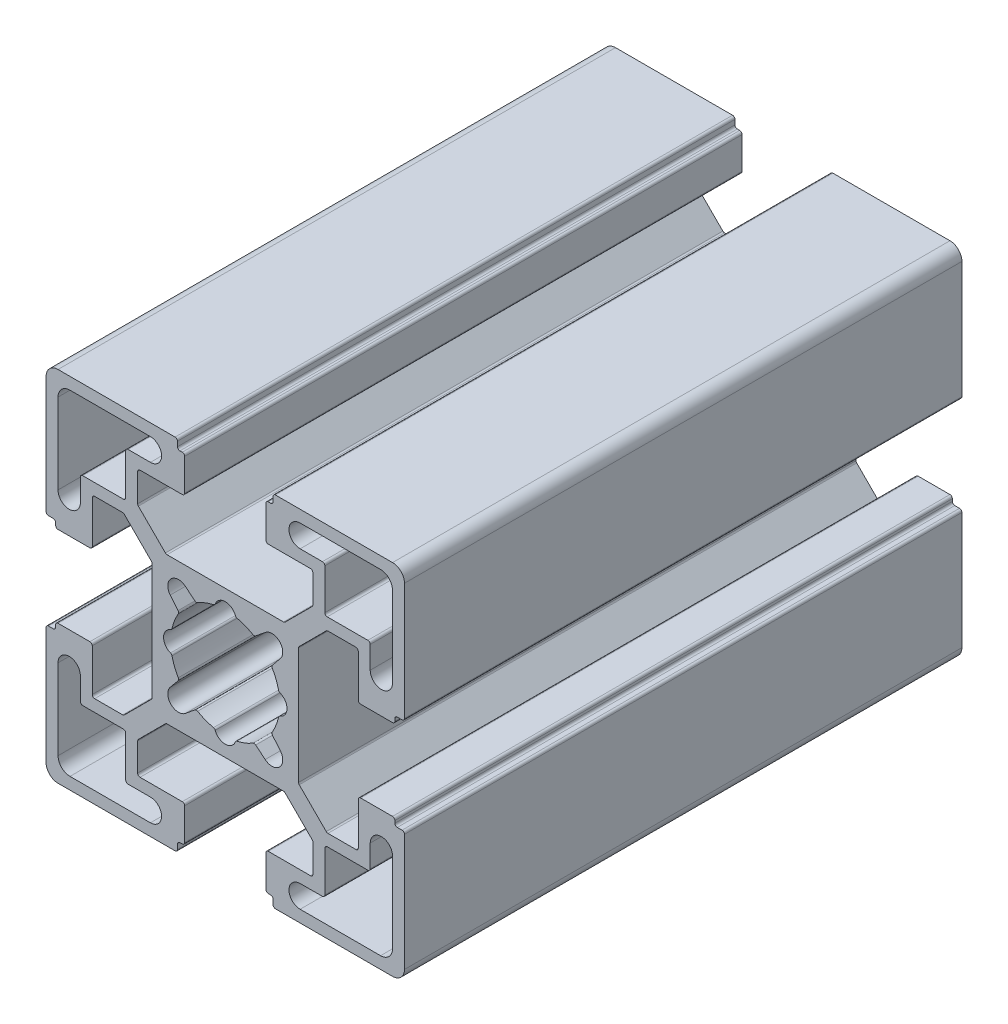
SolidWorks part; units mm, degrees
material "6063-T5"
ref_plane "Plane1" through (0, 0, 0) normal (0, 0, 1) x (1, 0, 0)
ref_plane "Plane2" through (0, 0, 0) normal (0, 1, 0) x (1, 0, 0)
ref_plane "Plane3" through (0, 0, 0) normal (1, 0, 0) x (0, 0, -1)
sketch "Sketch1" plane through (0, 0, 0) normal (0, 0, 1) x (1, 0, 0)
  line L0 (-3.8182, 5.9298) -> (-5.0112, 6.9114)
  line L1 (-6.9114, 5.0112) -> (-5.9298, 3.8182)
  line L2 (-5.9298, -3.8182) -> (-6.9114, -5.0112)
  line L3 (-5.0112, -6.9114) -> (-3.8182, -5.9298)
  line L4 (3.8182, -5.9298) -> (5.0112, -6.9114)
  line L5 (6.9114, -5.0112) -> (5.9298, -3.8182)
  line L6 (5.9298, 3.8182) -> (6.9114, 5.0112)
  line L7 (5.0112, 6.9114) -> (3.8182, 5.9298)
  line L8 (-19.5, -21) -> (-9.4, -21)
  line L9 (-9.4, -18.2) -> (-12.2, -18.2)
  line L10 (-12.5, -17.9) -> (-12.5, -12.8)
  line L11 (-12.8, -12.5) -> (-17.9, -12.5)
  line L12 (-18.2, -12.2) -> (-18.2, -9.4)
  line L13 (-21, -9.4) -> (-21, -19.5)
  line L14 (17.9, -12.5) -> (12.8, -12.5)
  line L15 (12.5, -12.8) -> (12.5, -17.9)
  line L16 (12.2, -18.2) -> (9.4, -18.2)
  line L17 (9.4, -21) -> (19.5, -21)
  line L18 (21, -19.5) -> (21, -9.4)
  line L19 (18.2, -9.4) -> (18.2, -12.2)
  line L20 (19.5, 21) -> (9.4, 21)
  line L21 (9.4, 18.2) -> (12.2, 18.2)
  line L22 (12.5, 17.9) -> (12.5, 12.8)
  line L23 (12.8, 12.5) -> (17.9, 12.5)
  line L24 (18.2, 12.2) -> (18.2, 9.4)
  line L25 (21, 9.4) -> (21, 19.5)
  line L26 (-18.2, 9.4) -> (-18.2, 12.2)
  line L27 (-17.9, 12.5) -> (-12.8, 12.5)
  line L28 (-12.5, 12.8) -> (-12.5, 17.9)
  line L29 (-12.2, 18.2) -> (-9.4, 18.2)
  line L30 (-9.4, 21) -> (-19.5, 21)
  line L31 (-21, 19.5) -> (-21, 9.4)
  line L32 (22.5, 6.3) -> (22.5, 21)
  line L33 (21.6, 6) -> (22.2, 6)
  line L34 (21.3, 5.4) -> (21.3, 5.7)
  line L36 (16.7, 10.7) -> (16.7, 5.4)
  line L37 (12.892, 11) -> (16.4, 11)
  line L38 (9.2879, 7.5201) -> (12.6799, 10.9121)
  line L39 (9.2, -7.308) -> (9.2, 7.308)
  line L40 (12.6799, -10.9121) -> (9.2879, -7.5201)
  line L41 (16.4, -11) -> (12.892, -11)
  line L42 (16.7, -5.4) -> (16.7, -10.7)
  line L44 (21.3, -5.7) -> (21.3, -5.4)
  line L45 (22.2, -6) -> (21.6, -6)
  line L46 (22.5, -21) -> (22.5, -6.3)
  line L47 (6.3, -22.5) -> (21, -22.5)
  line L48 (6, -21.6) -> (6, -22.2)
  line L49 (5.4, -21.3) -> (5.7, -21.3)
  line L51 (10.7, -16.7) -> (5.4, -16.7)
  line L52 (11, -12.892) -> (11, -16.4)
  line L53 (7.5201, -9.2879) -> (10.9121, -12.6799)
  line L54 (-7.4322, -9.2) -> (7.308, -9.2)
  line L55 (-10.9121, -12.6799) -> (-7.4322, -9.2)
  line L56 (-11, -16.4) -> (-11, -12.892)
  line L57 (-5.4, -16.7) -> (-10.7, -16.7)
  line L59 (-5.7, -21.3) -> (-5.4, -21.3)
  line L60 (-6, -22.2) -> (-6, -21.6)
  line L61 (-21, -22.5) -> (-6.3, -22.5)
  line L62 (-22.5, -6.3) -> (-22.5, -21)
  line L63 (-21.6, -6) -> (-22.2, -6)
  line L64 (-21.3, -5.4) -> (-21.3, -5.7)
  line L66 (-16.7, -10.7) -> (-16.7, -5.4)
  line L67 (-12.892, -11) -> (-16.4, -11)
  line L68 (-9.2879, -7.5201) -> (-12.6799, -10.9121)
  line L69 (-9.2, 7.308) -> (-9.2, -7.308)
  line L70 (-12.6799, 10.9121) -> (-9.2879, 7.5201)
  line L71 (-16.4, 11) -> (-12.892, 11)
  line L72 (-16.7, 5.4) -> (-16.7, 10.7)
  line L74 (-21.3, 5.7) -> (-21.3, 5.4)
  line L75 (-22.2, 6) -> (-21.6, 6)
  line L76 (-22.5, 21) -> (-22.5, 6.3)
  line L77 (-6.3, 22.5) -> (-21, 22.5)
  line L78 (-6, 21.6) -> (-6, 22.2)
  line L79 (-5.4, 21.3) -> (-5.7, 21.3)
  line L81 (-10.7, 16.7) -> (-5.4, 16.7)
  line L82 (-11, 12.892) -> (-11, 16.4)
  line L83 (-7.5201, 9.2879) -> (-10.9121, 12.6799)
  line L84 (7.308, 9.2) -> (-7.308, 9.2)
  line L85 (10.9121, 12.6799) -> (7.5201, 9.2879)
  line L86 (11, 16.4) -> (11, 12.892)
  line L87 (5.4, 16.7) -> (10.7, 16.7)
  line L89 (5.7, 21.3) -> (5.4, 21.3)
  line L90 (6, 22.2) -> (6, 21.6)
  line L91 (21, 22.5) -> (6.3, 22.5)
  line L92 (-5.1, 17) -> (-5.1, 21)
  line L93 (-21, 5.1) -> (-17, 5.1)
  line L94 (-17, -5.1) -> (-21, -5.1)
  line L95 (-5.1, -21) -> (-5.1, -17)
  line L96 (5.1, -17) -> (5.1, -21)
  line L97 (21, -5.1) -> (17, -5.1)
  line L98 (17, 5.1) -> (21, 5.1)
  line L99 (5.1, 21) -> (5.1, 17)
  arc A0 (-1.4794, 6.6883) -> (-1.2635, 6.8756) centre (-1.5442, 6.9813) ccw
  arc A1 (-1.4794, 6.6883) -> (-3.4754, 5.9029) centre (0, 0) ccw
  arc A2 (-3.8182, 5.9298) -> (-3.4754, 5.9029) centre (-3.6276, 6.1614) ccw
  arc A3 (-5.0112, 6.9114) -> (-6.9114, 5.0112) centre (-5.869, 5.869) ccw
  arc A4 (-5.9029, 3.4754) -> (-5.9298, 3.8182) centre (-6.1614, 3.6276) ccw
  arc A5 (-5.9029, 3.4754) -> (-6.6883, 1.4794) centre (0, 0) ccw
  arc A6 (-6.8756, 1.2635) -> (-6.6883, 1.4794) centre (-6.9813, 1.5442) ccw
  arc A7 (-6.8756, 1.2635) -> (-6.8756, -1.2635) centre (-6.4, 0) ccw
  arc A8 (-6.6883, -1.4794) -> (-6.8756, -1.2635) centre (-6.9813, -1.5442) ccw
  arc A9 (-6.6883, -1.4794) -> (-5.9029, -3.4754) centre (0, 0) ccw
  arc A10 (-5.9298, -3.8182) -> (-5.9029, -3.4754) centre (-6.1614, -3.6276) ccw
  arc A11 (-6.9114, -5.0112) -> (-5.0112, -6.9114) centre (-5.869, -5.869) ccw
  arc A12 (-3.4754, -5.9029) -> (-3.8182, -5.9298) centre (-3.6276, -6.1614) ccw
  arc A13 (-3.4754, -5.9029) -> (-1.4794, -6.6883) centre (0, 0) ccw
  arc A14 (-1.2635, -6.8756) -> (-1.4794, -6.6883) centre (-1.5442, -6.9812) ccw
  arc A15 (-1.2635, -6.8756) -> (1.2635, -6.8756) centre (0, -6.4) ccw
  arc A16 (1.4794, -6.6883) -> (1.2635, -6.8756) centre (1.5442, -6.9812) ccw
  arc A17 (1.4794, -6.6883) -> (3.4754, -5.9029) centre (0, 0) ccw
  arc A18 (3.8182, -5.9298) -> (3.4754, -5.9029) centre (3.6276, -6.1614) ccw
  arc A19 (5.0112, -6.9114) -> (6.9114, -5.0112) centre (5.869, -5.869) ccw
  arc A20 (5.9029, -3.4754) -> (5.9298, -3.8182) centre (6.1614, -3.6276) ccw
  arc A21 (5.9029, -3.4754) -> (6.6883, -1.4794) centre (0, 0) ccw
  arc A22 (6.8756, -1.2635) -> (6.6883, -1.4794) centre (6.9812, -1.5442) ccw
  arc A23 (6.8756, -1.2635) -> (6.8756, 1.2635) centre (6.4, 0) ccw
  arc A24 (6.6883, 1.4794) -> (6.8756, 1.2635) centre (6.9812, 1.5442) ccw
  arc A25 (6.6883, 1.4794) -> (5.9029, 3.4754) centre (0, 0) ccw
  arc A26 (5.9298, 3.8182) -> (5.9029, 3.4754) centre (6.1614, 3.6276) ccw
  arc A27 (6.9114, 5.0112) -> (5.0112, 6.9114) centre (5.869, 5.869) ccw
  arc A28 (3.4754, 5.9029) -> (3.8182, 5.9298) centre (3.6276, 6.1614) ccw
  arc A29 (3.4754, 5.9029) -> (1.4794, 6.6883) centre (0, 0) ccw
  arc A30 (1.2635, 6.8756) -> (1.4794, 6.6883) centre (1.5442, 6.9813) ccw
  arc A31 (1.2635, 6.8756) -> (-1.2635, 6.8756) centre (0, 6.4) ccw
  arc A32 (-21, -19.5) -> (-19.5, -21) centre (-19.5, -19.5) ccw
  arc A33 (-9.4, -21) -> (-9.4, -18.2) centre (-9.4, -19.6) ccw
  arc A34 (-12.5, -17.9) -> (-12.2, -18.2) centre (-12.2, -17.9) ccw
  arc A35 (-12.5, -12.8) -> (-12.8, -12.5) centre (-12.8, -12.8) ccw
  arc A36 (-18.2, -12.2) -> (-17.9, -12.5) centre (-17.9, -12.2) ccw
  arc A37 (-18.2, -9.4) -> (-21, -9.4) centre (-19.6, -9.4) ccw
  arc A38 (17.9, -12.5) -> (18.2, -12.2) centre (17.9, -12.2) ccw
  arc A39 (12.8, -12.5) -> (12.5, -12.8) centre (12.8, -12.8) ccw
  arc A40 (12.2, -18.2) -> (12.5, -17.9) centre (12.2, -17.9) ccw
  arc A41 (9.4, -18.2) -> (9.4, -21) centre (9.4, -19.6) ccw
  arc A42 (19.5, -21) -> (21, -19.5) centre (19.5, -19.5) ccw
  arc A43 (21, -9.4) -> (18.2, -9.4) centre (19.6, -9.4) ccw
  arc A44 (21, 19.5) -> (19.5, 21) centre (19.5, 19.5) ccw
  arc A45 (9.4, 21) -> (9.4, 18.2) centre (9.4, 19.6) ccw
  arc A46 (12.5, 17.9) -> (12.2, 18.2) centre (12.2, 17.9) ccw
  arc A47 (12.5, 12.8) -> (12.8, 12.5) centre (12.8, 12.8) ccw
  arc A48 (18.2, 12.2) -> (17.9, 12.5) centre (17.9, 12.2) ccw
  arc A49 (18.2, 9.4) -> (21, 9.4) centre (19.6, 9.4) ccw
  arc A50 (-21, 9.4) -> (-18.2, 9.4) centre (-19.6, 9.4) ccw
  arc A51 (-17.9, 12.5) -> (-18.2, 12.2) centre (-17.9, 12.2) ccw
  arc A52 (-12.8, 12.5) -> (-12.5, 12.8) centre (-12.8, 12.8) ccw
  arc A53 (-12.2, 18.2) -> (-12.5, 17.9) centre (-12.2, 17.9) ccw
  arc A54 (-9.4, 18.2) -> (-9.4, 21) centre (-9.4, 19.6) ccw
  arc A55 (-19.5, 21) -> (-21, 19.5) centre (-19.5, 19.5) ccw
  arc A56 (22.2, 6) -> (22.5, 6.3) centre (22.2, 6.3) ccw
  arc A57 (21.6, 6) -> (21.3, 5.7) centre (21.6, 5.7) ccw
  arc A58 (-17, -5.1) -> (-16.7, -5.4) centre (-17, -5.4) cw
  arc A59 (16.7, 10.7) -> (16.4, 11) centre (16.4, 10.7) ccw
  arc A60 (12.892, 11) -> (12.6799, 10.9121) centre (12.892, 10.7) ccw
  arc A61 (9.2879, 7.5201) -> (9.2, 7.308) centre (9.5, 7.308) ccw
  arc A62 (9.2, -7.308) -> (9.2879, -7.5201) centre (9.5, -7.308) ccw
  arc A63 (12.6799, -10.9121) -> (12.892, -11) centre (12.892, -10.7) ccw
  arc A64 (16.4, -11) -> (16.7, -10.7) centre (16.4, -10.7) ccw
  arc A65 (-17, 5.1) -> (-16.7, 5.4) centre (-17, 5.4) ccw
  arc A66 (21.3, -5.7) -> (21.6, -6) centre (21.6, -5.7) ccw
  arc A67 (22.5, -6.3) -> (22.2, -6) centre (22.2, -6.3) ccw
  arc A68 (21, -22.5) -> (22.5, -21) centre (21, -21) ccw
  arc A69 (6, -22.2) -> (6.3, -22.5) centre (6.3, -22.2) ccw
  arc A70 (6, -21.6) -> (5.7, -21.3) centre (5.7, -21.6) ccw
  arc A71 (-5.1, 17) -> (-5.4, 16.7) centre (-5.4, 17) cw
  arc A72 (10.7, -16.7) -> (11, -16.4) centre (10.7, -16.4) ccw
  arc A73 (11, -12.892) -> (10.9121, -12.6799) centre (10.7, -12.892) ccw
  arc A74 (7.5201, -9.2879) -> (7.308, -9.2) centre (7.308, -9.5) ccw
  arc A75 (-10.9121, -12.6799) -> (-11, -12.892) centre (-10.7, -12.892) ccw
  arc A76 (-11, -16.4) -> (-10.7, -16.7) centre (-10.7, -16.4) ccw
  arc A77 (5.1, 17) -> (5.4, 16.7) centre (5.4, 17) ccw
  arc A78 (-5.7, -21.3) -> (-6, -21.6) centre (-5.7, -21.6) ccw
  arc A79 (-6.3, -22.5) -> (-6, -22.2) centre (-6.3, -22.2) ccw
  arc A80 (-22.5, -21) -> (-21, -22.5) centre (-21, -21) ccw
  arc A81 (-22.2, -6) -> (-22.5, -6.3) centre (-22.2, -6.3) ccw
  arc A82 (-21.6, -6) -> (-21.3, -5.7) centre (-21.6, -5.7) ccw
  arc A83 (16.7, 5.4) -> (17, 5.1) centre (17, 5.4) ccw
  arc A84 (-16.7, -10.7) -> (-16.4, -11) centre (-16.4, -10.7) ccw
  arc A85 (-12.892, -11) -> (-12.6799, -10.9121) centre (-12.892, -10.7) ccw
  arc A86 (-9.2879, -7.5201) -> (-9.2, -7.308) centre (-9.5, -7.308) ccw
  arc A87 (-9.2, 7.308) -> (-9.2879, 7.5201) centre (-9.5, 7.308) ccw
  arc A88 (-12.6799, 10.9121) -> (-12.892, 11) centre (-12.892, 10.7) ccw
  arc A89 (-16.4, 11) -> (-16.7, 10.7) centre (-16.4, 10.7) ccw
  arc A90 (17, -5.1) -> (16.7, -5.4) centre (17, -5.4) ccw
  arc A91 (-21.3, 5.7) -> (-21.6, 6) centre (-21.6, 5.7) ccw
  arc A92 (-22.5, 6.3) -> (-22.2, 6) centre (-22.2, 6.3) ccw
  arc A93 (-21, 22.5) -> (-22.5, 21) centre (-21, 21) ccw
  arc A94 (-6, 22.2) -> (-6.3, 22.5) centre (-6.3, 22.2) ccw
  arc A95 (-6, 21.6) -> (-5.7, 21.3) centre (-5.7, 21.6) ccw
  arc A96 (5.1, -17) -> (5.4, -16.7) centre (5.4, -17) cw
  arc A97 (-10.7, 16.7) -> (-11, 16.4) centre (-10.7, 16.4) ccw
  arc A98 (-11, 12.892) -> (-10.9121, 12.6799) centre (-10.7, 12.892) ccw
  arc A99 (-7.5201, 9.2879) -> (-7.308, 9.2) centre (-7.308, 9.5) ccw
  arc A100 (7.308, 9.2) -> (7.5201, 9.2879) centre (7.308, 9.5) ccw
  arc A101 (10.9121, 12.6799) -> (11, 12.892) centre (10.7, 12.892) ccw
  arc A102 (11, 16.4) -> (10.7, 16.7) centre (10.7, 16.4) ccw
  arc A103 (-5.1, -17) -> (-5.4, -16.7) centre (-5.4, -17) ccw
  arc A104 (5.7, 21.3) -> (6, 21.6) centre (5.7, 21.6) ccw
  arc A105 (6.3, 22.5) -> (6, 22.2) centre (6.3, 22.2) ccw
  arc A106 (22.5, 21) -> (21, 22.5) centre (21, 21) ccw
  arc A107 (-21, 5.1) -> (-21.3, 5.4) centre (-21, 5.4) cw
  arc A108 (-21, -5.1) -> (-21.3, -5.4) centre (-21, -5.4) ccw
  arc A109 (-5.1, -21) -> (-5.4, -21.3) centre (-5.4, -21) cw
  arc A110 (5.1, -21) -> (5.4, -21.3) centre (5.4, -21) ccw
  arc A111 (21, -5.1) -> (21.3, -5.4) centre (21, -5.4) cw
  arc A112 (21, 5.1) -> (21.3, 5.4) centre (21, 5.4) ccw
  arc A113 (5.1, 21) -> (5.4, 21.3) centre (5.4, 21) cw
  arc A114 (-5.1, 21) -> (-5.4, 21.3) centre (-5.4, 21) ccw
  point P299 (0, 22.5)
  point P300 (22.5, 22.5)
  point P301 (-22.5, 22.5)
  point P302 (-22.5, 0)
  point P303 (-22.5, -22.5)
  point P304 (0, -22.5)
  point P305 (22.5, -22.5)
  point P306 (22.5, 0)
  point P308 (0, 0)
  dimension "D1" = 0.3
extrude "Ressalto-extrusão2" add sketch "Sketch1" along normal blind 70 contours L32 A106 L91 A105 L90 A104 L89 L99 A77 L87 A102 L86 A101 L85 A100 L84 A99 L83 A98 L82 A97 L81 A71 L92 L79 A95 L78 A94 L77 A93 L76 A92 L75 A91 L74 L93 A65 L72 A89 L71 A88 L70 A87 L69 A86 L68 A85 L67 A84 L66 A58 region at (21.9621, 6.5379, 0)
